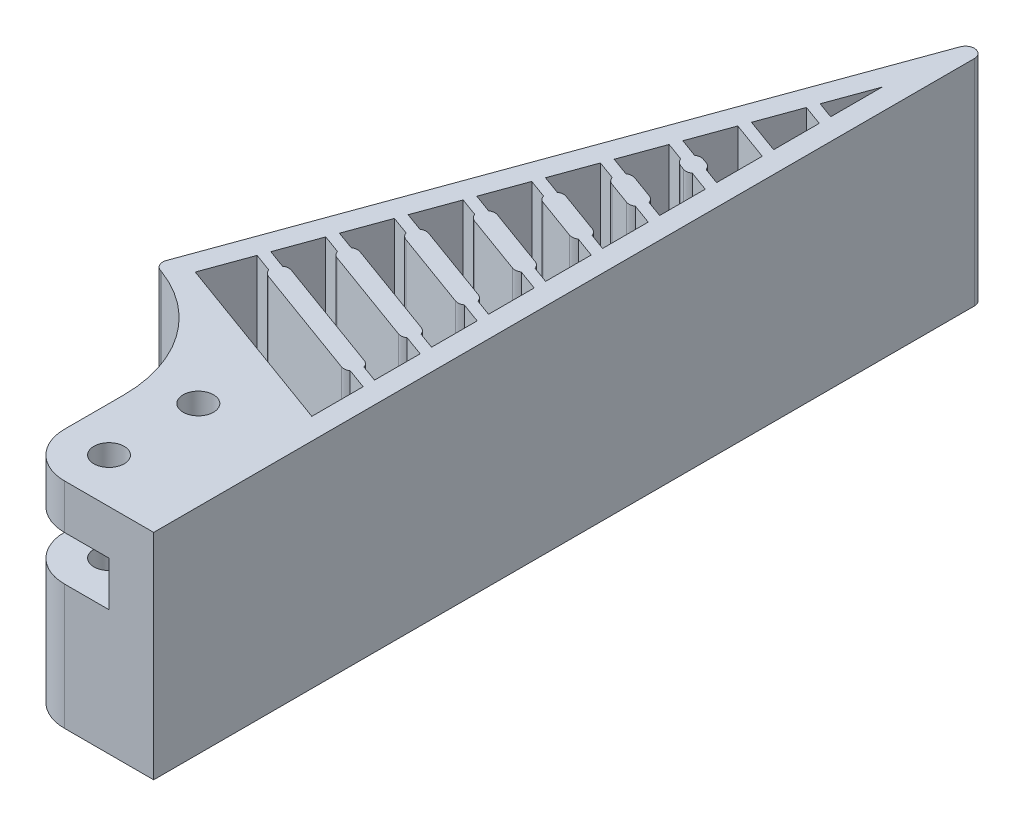
SolidWorks part; units mm, degrees
ref_plane "前视基准面" through (0, 0, 0) normal (0, 0, 1) x (1, 0, 0)
ref_plane "上视基准面" through (0, 0, 0) normal (0, 1, 0) x (1, 0, 0)
ref_plane "右视基准面" through (0, 0, 0) normal (1, 0, 0) x (0, 0, -1)
sketch "草图1" plane through (0, 0, 0) normal (0, 1, 0) x (1, 0, 0)
  line L0 (0, 0) -> (0, 10) construction
  line L1 (-5, 0) -> (-5, 17.1407)
  line L2 (0, -5) -> (10, -5)
  line L4 (-15.9973, 21.1434) -> (10, 92.5705)
  line L12 (10, 92.5705) -> (10, 11.6812)
  line L13 (10, 11.6812) -> (10, -5)
  line L15 (-12.9212, 22.5779) -> (7.6, 78.9594)
  line L16 (7.6, 78.9594) -> (7.6, 15.1087)
  line L17 (7.6, 15.1087) -> (-12.9212, 22.5779)
  line L18 (-10.8691, 28.216) -> (-8.05, 27.1899) construction
  line L19 (-8.05, 27.1899) -> (4.7809, 22.5199) construction
  line L20 (4.7809, 22.5199) -> (7.6, 21.4938) construction
  line L21 (-8.05, 27.1899) -> (4.7809, 22.5199) construction
  line L24 (-7.708, 28.1296) -> (5.1229, 23.4596)
  line L25 (-8.392, 26.2503) -> (4.4389, 21.5802)
  line L26 (-10.6639, 28.7798) -> (-8.5966, 28.0274)
  line L27 (-11.0743, 27.6522) -> (-9.007, 26.8997)
  line L28 (5.7379, 22.8101) -> (7.6, 22.1323)
  line L29 (5.3275, 21.6824) -> (7.6, 20.8553)
  line L30 (-8.817, 33.8542) -> (-5.9979, 32.8281) construction
  line L31 (-5.9979, 32.8281) -> (4.7809, 28.9049) construction
  line L32 (4.7809, 28.9049) -> (7.6, 27.8789) construction
  line L33 (-5.9979, 32.8281) -> (4.7809, 28.9049) construction
  line L34 (-5.6559, 33.7678) -> (5.1229, 29.8446)
  line L35 (-6.3399, 31.8884) -> (4.4389, 27.9652)
  line L36 (-8.6118, 34.418) -> (-6.5444, 33.6655)
  line L37 (-9.0222, 33.2903) -> (-6.9549, 32.5379)
  line L38 (5.7379, 29.1951) -> (7.6, 28.5174)
  line L39 (5.3275, 28.0675) -> (7.6, 27.2404)
  line L40 (-6.7648, 39.4923) -> (-3.9458, 38.4663) construction
  line L41 (-3.9458, 38.4663) -> (4.7809, 35.29) construction
  line L42 (4.7809, 35.29) -> (7.6, 34.2639) construction
  line L43 (-3.9458, 38.4663) -> (4.7809, 35.29) construction
  line L44 (-3.6037, 39.406) -> (5.1229, 36.2297)
  line L45 (-4.2878, 37.5266) -> (4.4389, 34.3503)
  line L46 (-6.5596, 40.0561) -> (-4.4923, 39.3037)
  line L47 (-6.9701, 38.9285) -> (-4.9027, 38.1761)
  line L48 (5.7379, 35.5802) -> (7.6, 34.9024)
  line L49 (5.3275, 34.4526) -> (7.6, 33.6254)
  line L50 (-4.7127, 45.1305) -> (-1.8936, 44.1044) construction
  line L51 (-1.8936, 44.1044) -> (4.7809, 41.6751) construction
  line L52 (4.7809, 41.6751) -> (7.6, 40.649) construction
  line L53 (-1.8936, 44.1044) -> (4.7809, 41.6751) construction
  line L56 (-1.5516, 45.0441) -> (5.1229, 42.6148)
  line L57 (-2.2357, 43.1647) -> (4.4389, 40.7354)
  line L58 (-4.5075, 45.6943) -> (-2.4402, 44.9418)
  line L59 (-4.9179, 44.5667) -> (-2.8506, 43.8142)
  line L60 (-5, 17.1407) -> (10, 11.6812) construction
  line L70 (5.7379, 41.9653) -> (7.6, 41.2875)
  line L71 (5.3275, 40.8376) -> (7.6, 40.0105)
  line L72 (-12.9212, 22.5779) -> (7.6, 15.1087) construction
  line L73 (-15.9973, 21.1434) -> (10, 11.6812) construction
  line L74 (-15.9973, 21.1434) -> (-5, 17.1407)
  line L76 (10, 11.6812) -> (-5, 11.6812) construction
  line L77 (-2.6606, 50.7686) -> (0.1585, 49.7426) construction
  line L78 (0.1585, 49.7426) -> (4.7809, 48.0601) construction
  line L79 (4.7809, 48.0601) -> (7.6, 47.0341) construction
  line L80 (0.1585, 49.7426) -> (4.7809, 48.0601) construction
  line L81 (0.5005, 50.6823) -> (5.1229, 48.9998)
  line L82 (-0.1835, 48.8029) -> (4.4389, 47.1204)
  line L83 (-2.4554, 51.3324) -> (-0.3881, 50.58)
  line L84 (-2.8658, 50.2048) -> (-0.7985, 49.4524)
  line L85 (5.7379, 48.3503) -> (7.6, 47.6726)
  line L86 (5.3275, 47.2227) -> (7.6, 46.3956)
  line L87 (-0.6085, 56.4068) -> (2.2106, 55.3807) construction
  line L88 (2.2106, 55.3807) -> (4.7809, 54.4452) construction
  line L89 (4.7809, 54.4452) -> (7.6, 53.4191) construction
  line L90 (2.2106, 55.3807) -> (4.7809, 54.4452) construction
  line L91 (2.5526, 56.3204) -> (5.1229, 55.3849)
  line L92 (1.8686, 54.441) -> (4.4389, 53.5055)
  line L93 (-0.4033, 56.9706) -> (1.6641, 56.2182)
  line L94 (-0.8137, 55.843) -> (1.2536, 55.0905)
  line L95 (5.7379, 54.7354) -> (7.6, 54.0576)
  line L96 (5.3275, 53.6078) -> (7.6, 52.7806)
  line L97 (1.4436, 62.0449) -> (4.2627, 61.0189) construction
  line L98 (4.2627, 61.0189) -> (4.7809, 60.8303) construction
  line L99 (4.7809, 60.8303) -> (7.6, 59.8042) construction
  line L100 (4.2627, 61.0189) -> (4.7809, 60.8303) construction
  line L101 (4.6047, 61.9586) -> (5.1229, 61.77)
  line L102 (3.9207, 60.0792) -> (4.4389, 59.8906)
  line L103 (1.6488, 62.6088) -> (3.7162, 61.8563)
  line L104 (1.2384, 61.4811) -> (3.3057, 60.7287)
  line L105 (5.7379, 61.1205) -> (7.6, 60.4427)
  line L106 (5.3275, 59.9928) -> (7.6, 59.1657)
  line L107 (3.4958, 67.6831) -> (7.6, 66.1893) construction
  line L108 (5.5479, 73.3213) -> (7.6, 72.5743) construction
  line L111 (5.3427, 72.7574) -> (7.6, 71.9358)
  line L112 (3.2905, 67.1193) -> (7.6, 65.5508)
  line L114 (5.7531, 73.8851) -> (7.6, 73.2128)
  line L115 (3.701, 68.2469) -> (7.6, 66.8278)
  line L116 (3.701, 68.2469) -> (7.8052, 66.7531) construction
  line L117 (3.2905, 67.1193) -> (7.3948, 65.6255) construction
  line L118 (5.7531, 73.8851) -> (7.8052, 73.1382) construction
  line L119 (5.3427, 72.7574) -> (7.3948, 72.0105) construction
  circle A0 centre (0, 0) radius 1.7
  circle A1 centre (0, 10) radius 1.7
  arc A2 (-5, 0) -> (0, -5) centre (0, 0) ccw
  arc A5 (-7.708, 28.1296) -> (-8.392, 26.2503) centre (-8.05, 27.1899) ccw
  arc A6 (4.4389, 21.5802) -> (5.1229, 23.4596) centre (4.7809, 22.5199) ccw
  arc A7 (-5.6559, 33.7678) -> (-6.3399, 31.8884) centre (-5.9979, 32.8281) ccw
  arc A8 (4.4389, 27.9652) -> (5.1229, 29.8446) centre (4.7809, 28.9049) ccw
  arc A9 (-3.6037, 39.406) -> (-4.2878, 37.5266) centre (-3.9458, 38.4663) ccw
  arc A10 (4.4389, 34.3503) -> (5.1229, 36.2297) centre (4.7809, 35.29) ccw
  arc A17 (-1.5516, 45.0441) -> (-2.2357, 43.1647) centre (-1.8936, 44.1044) ccw
  arc A18 (4.4389, 40.7354) -> (5.1229, 42.6148) centre (4.7809, 41.6751) ccw
  arc A19 (0.5005, 50.6823) -> (-0.1835, 48.8029) centre (0.1585, 49.7426) ccw
  arc A20 (4.4389, 47.1204) -> (5.1229, 48.9998) centre (4.7809, 48.0601) ccw
  arc A21 (2.5526, 56.3204) -> (1.8686, 54.441) centre (2.2106, 55.3807) ccw
  arc A22 (4.4389, 53.5055) -> (5.1229, 55.3849) centre (4.7809, 54.4452) ccw
  arc A23 (4.6047, 61.9586) -> (3.9207, 60.0792) centre (4.2627, 61.0189) ccw
  arc A24 (4.4389, 59.8906) -> (5.1229, 61.77) centre (4.7809, 60.8303) ccw
  circle A25 centre (0, 10) radius 5 construction
  point P17 (-1.6345, 24.8549)
  point P35 (-0.6085, 30.8665)
  point P50 (2.4697, 48.9014)
  point P62 (0.4176, 36.8781)
  point P88 (1.4436, 42.8897)
  point P122 (6.5739, 72.9478)
  point P124 (-1.4217, 50.9562)
  point P131 (3.4958, 54.913)
  point P156 (4.5218, 60.9246)
  dimension "D1" = 3.4
  dimension "D3" = 5
  dimension "D6" = 2.4
  dimension "D5" = 10
  dimension "D2" = 10
  dimension "D7" = 20
  dimension "D8" = 2
  dimension "D9" = 0.6
  dimension "D10" = 0.6
  dimension "D11" = 0.6
  dimension "D12" = 0.6
  dimension "D13" = 3
  dimension "D14" = 3
  dimension "D15" = 6
  dimension "D16" = 0.6
  dimension "D17" = 0.6
  dimension "D18" = 0.6
  dimension "D19" = 0.6
  dimension "D20" = 3
  dimension "D21" = 2
  dimension "D22" = 6
  dimension "D23" = 60
  dimension "D24" = 0.6
  dimension "D25" = 0.6
  dimension "D26" = 0.6
  dimension "D27" = 0.6
  dimension "D28" = 2
  dimension "D29" = 6
  dimension "D30" = 6
  dimension "D31" = 0.6
  dimension "D32" = 3
  dimension "D33" = 0.6
  dimension "D34" = 2
  dimension "D35" = 0.6
  dimension "D36" = 0.6
  dimension "D37" = 0.6
  dimension "D38" = 0.6
  dimension "D39" = 6
  dimension "D40" = 2
  dimension "D41" = 3
  dimension "D42" = 0.6
  dimension "D43" = 6
  dimension "D44" = 3
  dimension "D45" = 2
  dimension "D46" = 0.6
  dimension "D47" = 2
  dimension "D48" = 6
  dimension "D49" = 3
  dimension "D50" = 6
  dimension "D51" = 6
  dimension "D53" = 0.6
  dimension "D54" = 0.6
extrude "凸台-拉伸1" add sketch "草图1" along normal blind 24 contours L1 A2 L2 L13 L12 L4 L74 L16 L17 L15 | L114 L15 L111 L16 | L115 L15 L112 L16 | A23 L103 L15 L104 | A24 L101 A23 L102 | A24 L106 L16 L105 | A22 L96 L16 L95 | A22 L91 A21 L92 | A21 L93 L15 L94 | A19 L83 L15 L84 | A20 L81 A19 L82 | A20 L86 L16 L85 | A18 L71 L16 L70 | A18 L56 A17 L57 | A17 L58 L15 L59 | A9 L46 L15 L47 | A10 L44 A9 L45 | A10 L49 L16 L48 | A8 L39 L16 L38 | A8 L34 A7 L35 | A7 L36 L15 L37 | A5 L26 L15 L27 | A6 L24 A5 L25 | A6 L29 L16 L28 region at (-3.9903, 0, -8.5704) region at (-9.8987, 0, -27.8628) region at (-1.6345, 0, -24.8549) region at (6.626, 0, -21.8258) region at (-7.8465, 0, -33.501) region at (-0.6085, 0, -30.8665) region at (6.626, 0, -28.2109) region at (-5.7944, 0, -39.1391) region at (0.4176, 0, -36.8781) region at (6.626, 0, -34.5959) region at (-3.7423, 0, -44.7773) region at (1.4436, 0, -42.8897) region at (6.626, 0, -40.981) region at (-1.6902, 0, -50.4154) region at (2.4697, 0, -48.9014) region at (6.626, 0, -47.3661) region at (0.3619, 0, -56.0536) region at (3.4958, 0, -54.913) region at (6.626, 0, -53.7511) region at (2.4141, 0, -61.6917) region at (4.5218, 0, -60.9246) region at (6.626, 0, -60.1362) region at (5.5462, 0, -66.9262) region at (6.5705, 0, -72.9278)
sketch "草图2" plane through (0, 0, 0) normal (0, -1, 0) x (1, 0, 0)
  line L0 (-5, 0) -> (-5, -17.1407) construction
  line L1 (-5, -14.94) -> (5, -14.94)
  line L2 (-5, -14.94) -> (-5, 5)
  line L3 (-5, 5) -> (5, 5)
  line L4 (5, -14.94) -> (5, 5)
  line L5 (0, 5) -> (10, 5) construction
  line L6 (-5, -17.1407) -> (10, -11.6812) construction
  line L7 (10, -92.5705) -> (10, 5) construction
  line L8 (-15.9973, -21.1434) -> (-5, -17.1407) construction
  circle A0 centre (0, 0) radius 1.7 construction
  circle A1 centre (0, 0) radius 1.7
  circle A2 centre (0, -10) radius 1.7 construction
  circle A3 centre (0, -10) radius 1.7
  arc A4 (5, -10.14) -> (0.2, -14.94) centre (0.2, -10.14) cw
  point P14 (5, -4.97)
  dimension "D2" = 5
  dimension "D3" = 4.8
  dimension "D1" = 10
extrude "切除-拉伸1" cut sketch "草图2" against normal blind 5 from offset 14 contours A4 L4 L3 L2 L1 A3 A1 region at (-0.1102, 0, -4.7174) offset against normal yes
fillet "圆角1" radius 1 2 edges at (10, 12, -92.5705) (-15.9973, 12, -21.1434)
fillet "圆角2" radius 15 1 edges at (-5, 12, -17.1407)
